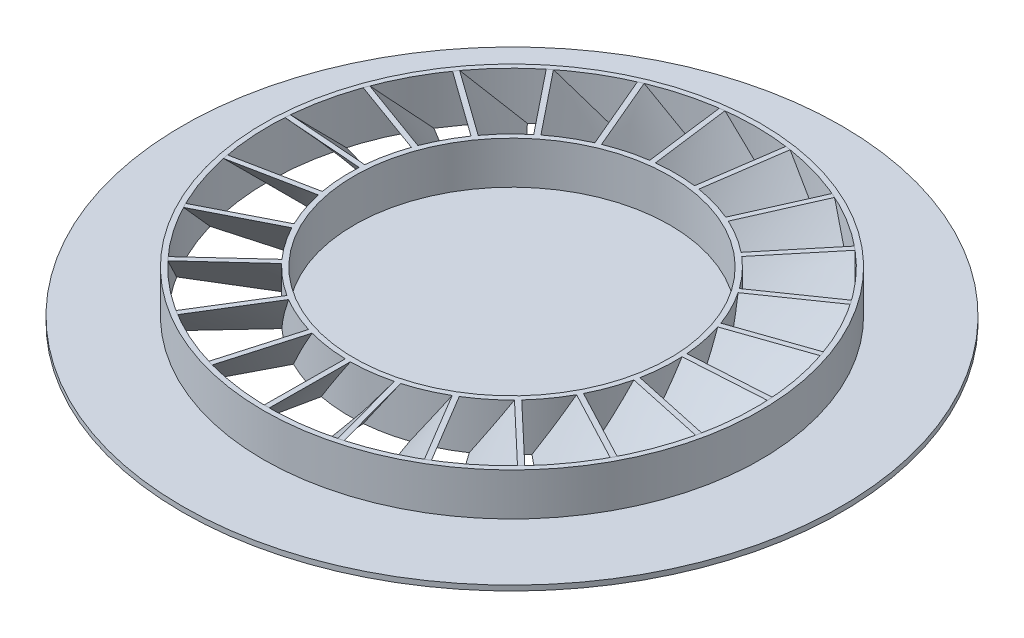
SolidWorks part; units mm, degrees
ref_plane "Front Plane" through (0, 0, 0) normal (0, 0, 1) x (1, 0, 0)
ref_plane "Top Plane" through (0, 0, 0) normal (0, 1, 0) x (1, 0, 0)
ref_plane "Right Plane" through (0, 0, 0) normal (1, 0, 0) x (0, 0, -1)
sketch "Sketch1" plane through (0, 0, 0) normal (0, 1, 0) x (1, 0, 0)
  circle A0 centre (0, 0) radius 33.25
  circle A1 centre (0, 0) radius 33.95
  circle A2 centre (0, 0) radius 45
  circle A3 centre (0, 0) radius 22.25
  circle A4 centre (0, 0) radius 21.55
  dimension "D1" = 66.5
  dimension "D2" = 0.7
  dimension "D3" = 90
  dimension "D4" = 44.5
  dimension "D5" = 0.7
extrude "Boss-Extrude1" add sketch "Sketch1" along normal blind 6.5 contours A1 A0 region at (-33.854, 0, 0)
extrude "Boss-Extrude2" add sketch "Sketch1<3>" along normal blind 0.7 contours A2 A1 region at (-43.7272, 0, 0)
sketch "Sketch1<3>" plane through (0, 0, 0) normal (0, 1, 0) x (1, 0, 0) same geometry as "Sketch1"
extrude "Boss-Extrude3" add sketch "Sketch1<4>" along normal blind 6.5 separate body contours A3 A4 region at (-21.6207, 0, 0)
sketch "Sketch1<4>" plane through (0, 0, 0) normal (0, 1, 0) x (1, 0, 0) same geometry as "Sketch1"
extrude "Boss-Extrude4" add sketch "Sketch1<5>" along normal blind 0.7 contours A4 region at (0, 0, 0)
sketch "Sketch1<5>" plane through (0, 0, 0) normal (0, 1, 0) x (1, 0, 0) same geometry as "Sketch1"
sketch "Sketch2" plane through (0, 0, 0) normal (0, -1, 0) x (1, 0, 0)
  line L0 (-31.9208, 9.3073) -> (-21.3278, 6.3393)
  line L1 (-33.2482, 0.35) -> (-22.2472, 0.35)
  line L2 (-33.2482, -0.35) -> (-22.2472, -0.35)
  line L3 (-32.1097, 8.6332) -> (-21.5167, 5.6652)
  line L4 (-28.226, 17.5743) -> (-18.8266, 11.8584)
  line L5 (-28.5897, 16.9762) -> (-19.1903, 11.2603)
  line L6 (-22.4378, 24.5378) -> (-14.9291, 16.498)
  line L7 (-22.9494, 24.0601) -> (-15.4407, 16.0202)
  line L8 (-14.9856, 29.6816) -> (-9.9244, 19.914)
  line L9 (-15.6071, 29.3595) -> (-10.5459, 19.592)
  line L10 (-6.4219, 32.624) -> (-4.1837, 21.8531)
  line L11 (-7.1072, 32.4815) -> (-4.869, 21.7107)
  line L12 (2.6181, 33.1468) -> (1.8674, 22.1715)
  line L13 (1.9198, 33.1945) -> (1.169, 22.2193)
  line L14 (11.4639, 31.2112) -> (7.7799, 20.8455)
  line L15 (10.8043, 31.4456) -> (7.1204, 21.0799)
  line L16 (19.4595, 26.9609) -> (13.1155, 17.9735)
  line L17 (18.8876, 27.3646) -> (12.5436, 18.3772)
  line L18 (26.0119, 20.711) -> (17.4783, 13.7685)
  line L19 (25.5701, 21.254) -> (17.0366, 14.3115)
  line L20 (30.635, 12.9251) -> (20.5449, 8.5423)
  line L21 (30.3561, 13.5671) -> (20.266, 9.1844)
  line L22 (32.9861, 4.1806) -> (22.0877, 2.6826)
  line L23 (32.8908, 4.874) -> (21.9924, 3.3761)
  line L24 (32.8908, -4.874) -> (21.9924, -3.3761)
  line L25 (32.9861, -4.1806) -> (22.0877, -2.6826)
  line L26 (30.3561, -13.5671) -> (20.266, -9.1844)
  line L27 (30.635, -12.9251) -> (20.5449, -8.5423)
  line L28 (25.5701, -21.254) -> (17.0366, -14.3115)
  line L29 (26.0119, -20.711) -> (17.4783, -13.7685)
  line L30 (18.8876, -27.3646) -> (12.5436, -18.3772)
  line L31 (19.4595, -26.9609) -> (13.1155, -17.9735)
  line L32 (10.8043, -31.4456) -> (7.1204, -21.0799)
  line L33 (11.4639, -31.2112) -> (7.7799, -20.8455)
  line L34 (1.9198, -33.1945) -> (1.169, -22.2193)
  line L35 (2.6181, -33.1468) -> (1.8674, -22.1715)
  line L36 (-7.1072, -32.4815) -> (-4.869, -21.7107)
  line L37 (-6.4219, -32.624) -> (-4.1837, -21.8531)
  line L38 (-15.6071, -29.3595) -> (-10.5459, -19.592)
  line L39 (-14.9856, -29.6816) -> (-9.9244, -19.914)
  line L40 (-22.9494, -24.0601) -> (-15.4407, -16.0202)
  line L41 (-22.4378, -24.5378) -> (-14.9291, -16.498)
  line L42 (-28.5897, -16.9762) -> (-19.1903, -11.2603)
  line L43 (-28.226, -17.5743) -> (-18.8266, -11.8584)
  line L44 (-32.1097, -8.6332) -> (-21.5167, -5.6652)
  line L45 (-31.9208, -9.3073) -> (-21.3278, -6.3393)
  circle A0 centre (0, 0) radius 33.25 construction
  circle A1 centre (0, 0) radius 22.25
  arc A2 (-21.3278, 6.3393) -> (-21.5167, 5.6652) centre (0, 0) ccw
  arc A3 (-18.8266, 11.8584) -> (-19.1903, 11.2603) centre (0, 0) ccw
  circle A5 centre (0, 0) radius 22.25 construction
  arc A6 (-31.9208, 9.3073) -> (-32.1097, 8.6332) centre (0, 0) ccw
  arc A7 (-28.226, 17.5743) -> (-28.5897, 16.9762) centre (0, 0) ccw
  arc A8 (-22.4378, 24.5378) -> (-22.9494, 24.0601) centre (0, 0) ccw
  arc A9 (-14.9291, 16.498) -> (-15.4407, 16.0202) centre (0, 0) ccw
  arc A10 (-9.9244, 19.914) -> (-10.5459, 19.592) centre (0, 0) ccw
  arc A11 (-14.9856, 29.6816) -> (-15.6071, 29.3595) centre (0, 0) ccw
  arc A12 (-6.4219, 32.624) -> (-7.1072, 32.4815) centre (0, 0) ccw
  arc A13 (-4.1837, 21.8531) -> (-4.869, 21.7107) centre (0, 0) ccw
  arc A14 (1.8674, 22.1715) -> (1.169, 22.2193) centre (0, 0) ccw
  arc A15 (2.6181, 33.1468) -> (1.9198, 33.1945) centre (0, 0) ccw
  arc A16 (11.4639, 31.2112) -> (10.8043, 31.4456) centre (0, 0) ccw
  arc A17 (7.7799, 20.8455) -> (7.1204, 21.0799) centre (0, 0) ccw
  arc A18 (13.1155, 17.9735) -> (12.5436, 18.3772) centre (0, 0) ccw
  arc A19 (19.4595, 26.9609) -> (18.8876, 27.3646) centre (0, 0) ccw
  arc A20 (26.0119, 20.711) -> (25.5701, 21.254) centre (0, 0) ccw
  arc A21 (17.4783, 13.7685) -> (17.0366, 14.3115) centre (0, 0) ccw
  arc A22 (20.5449, 8.5423) -> (20.266, 9.1844) centre (0, 0) ccw
  arc A23 (30.635, 12.9251) -> (30.3561, 13.5671) centre (0, 0) ccw
  arc A24 (32.9861, 4.1806) -> (32.8908, 4.874) centre (0, 0) ccw
  arc A25 (22.0877, 2.6826) -> (21.9924, 3.3761) centre (0, 0) ccw
  arc A26 (21.9924, -3.3761) -> (22.0877, -2.6826) centre (0, 0) ccw
  arc A27 (32.8908, -4.874) -> (32.9861, -4.1806) centre (0, 0) ccw
  arc A28 (-22.2472, 0.35) -> (-22.2472, -0.35) centre (0, 0) ccw
  arc A29 (-33.2482, 0.35) -> (-33.2482, -0.35) centre (0, 0) ccw
  arc A30 (-21.5167, -5.6652) -> (-21.3278, -6.3393) centre (0, 0) ccw
  arc A31 (-32.1097, -8.6332) -> (-31.9208, -9.3073) centre (0, 0) ccw
  arc A32 (-19.1903, -11.2603) -> (-18.8266, -11.8584) centre (0, 0) ccw
  arc A33 (-28.5897, -16.9762) -> (-28.226, -17.5743) centre (0, 0) ccw
  arc A34 (-22.9494, -24.0601) -> (-22.4378, -24.5378) centre (0, 0) ccw
  arc A35 (-15.4407, -16.0202) -> (-14.9291, -16.498) centre (0, 0) ccw
  arc A36 (-10.5459, -19.592) -> (-9.9244, -19.914) centre (0, 0) ccw
  arc A37 (-15.6071, -29.3595) -> (-14.9856, -29.6816) centre (0, 0) ccw
  arc A38 (-7.1072, -32.4815) -> (-6.4219, -32.624) centre (0, 0) ccw
  arc A39 (-4.869, -21.7107) -> (-4.1837, -21.8531) centre (0, 0) ccw
  arc A40 (1.169, -22.2193) -> (1.8674, -22.1715) centre (0, 0) ccw
  arc A41 (1.9198, -33.1945) -> (2.6181, -33.1468) centre (0, 0) ccw
  arc A42 (10.8043, -31.4456) -> (11.4639, -31.2112) centre (0, 0) ccw
  arc A43 (7.1204, -21.0799) -> (7.7799, -20.8455) centre (0, 0) ccw
  arc A44 (12.5436, -18.3772) -> (13.1155, -17.9735) centre (0, 0) ccw
  arc A45 (18.8876, -27.3646) -> (19.4595, -26.9609) centre (0, 0) ccw
  arc A46 (25.5701, -21.254) -> (26.0119, -20.711) centre (0, 0) ccw
  arc A47 (17.0366, -14.3115) -> (17.4783, -13.7685) centre (0, 0) ccw
  arc A48 (20.266, -9.1844) -> (20.5449, -8.5423) centre (0, 0) ccw
  arc A49 (30.3561, -13.5671) -> (30.635, -12.9251) centre (0, 0) ccw
  point P2 (-25.0222, 7.7008)
  point P14 (0, 0)
  point P106 (0, 0)
  dimension "D3" = 0.7
  dimension "D1" = 0
  dimension "D4" = 23
sketch "Sketch3" plane through (0, 6.5, 0) normal (0, 1, 0) x (1, 0, 0)
  line L0 (0, 0) -> (-32.6054, -6.5152) construction
  line L1 (0, 0) -> (-15.6581, 0) construction
  line L2 (-21.8846, -4.016) -> (-32.6722, -6.1716)
  line L3 (-21.7474, -4.7025) -> (-32.535, -6.8581)
  line L4 (-22.1565, 2.0373) -> (-33.1257, 2.8721)
  line L5 (-22.2097, 1.3393) -> (-33.1788, 2.1741)
  line L6 (-20.7853, 7.9395) -> (-31.1225, 11.7028)
  line L7 (-21.0247, 7.2817) -> (-31.3619, 11.045)
  line L8 (-17.8724, 13.2529) -> (-26.811, 19.6656)
  line L9 (-18.2805, 12.6841) -> (-27.219, 19.0968)
  line L10 (-13.6341, 17.5833) -> (-20.511, 26.1698)
  line L11 (-14.1805, 17.1457) -> (-21.0574, 25.7322)
  line L12 (-8.3846, 20.6097) -> (-12.6899, 30.7332)
  line L13 (-9.0288, 20.3358) -> (-13.3341, 30.4592)
  line L14 (-2.5132, 22.1076) -> (-3.9276, 33.0172)
  line L15 (-3.2074, 22.0176) -> (-4.6218, 32.9272)
  line L16 (3.5445, 21.9659) -> (5.126, 32.8525)
  line L17 (2.8518, 22.0665) -> (4.4332, 32.9531)
  line L18 (9.3394, 20.195) -> (13.7994, 30.2513)
  line L19 (8.6995, 20.4788) -> (13.1595, 30.5351)
  line L20 (14.4416, 16.9264) -> (21.4494, 25.4064)
  line L21 (13.902, 17.3723) -> (20.9098, 25.8524)
  line L22 (18.4728, 12.4024) -> (27.5085, 18.6773)
  line L23 (18.0735, 12.9774) -> (27.1093, 19.2523)
  line L24 (21.1339, 6.9586) -> (31.5275, 10.563)
  line L25 (20.9045, 7.6199) -> (31.2982, 11.2244)
  line L26 (22.2276, 0.9987) -> (33.2083, 1.6653)
  line L27 (22.1852, 1.6974) -> (33.1659, 2.364)
  line L28 (21.6728, -5.0353) -> (32.4261, -7.356)
  line L29 (21.8204, -4.351) -> (32.5738, -6.6717)
  line L30 (19.5106, -10.6958) -> (29.239, -15.8316)
  line L31 (19.8374, -10.0768) -> (29.5658, -15.2126)
  line L32 (15.9014, -15.563) -> (23.8835, -23.1332)
  line L33 (16.3831, -15.0551) -> (24.3652, -22.6252)
  line L34 (11.1129, -19.2761) -> (16.7565, -28.719)
  line L35 (11.7137, -18.917) -> (17.3574, -28.3599)
  line L36 (5.5001, -21.5595) -> (8.3869, -32.1749)
  line L37 (6.1756, -21.3758) -> (9.0623, -31.9912)
  line L38 (-0.5205, -22.2439) -> (-0.6048, -33.2445)
  line L39 (0.1795, -22.2493) -> (0.0952, -33.2499)
  line L40 (-6.5025, -21.2786) -> (-9.5516, -31.8485)
  line L41 (-5.83, -21.4726) -> (-8.8791, -32.0425)
  line L42 (-12.0023, -18.7352) -> (-17.7901, -28.0905)
  line L43 (-11.407, -19.1035) -> (-17.1948, -28.4588)
  line L44 (-16.6119, -14.8023) -> (-24.7091, -22.2491)
  line L45 (-16.1381, -15.3175) -> (-24.2352, -22.7644)
  line L46 (-19.9895, -9.7715) -> (-29.7956, -14.7576)
  line L47 (-19.6722, -10.3955) -> (-29.4783, -15.3816)
  circle A0 centre (0, 0) radius 33.25 construction
  circle A1 centre (0, 0) radius 22.25 construction
  arc A2 (-32.6722, -6.1716) -> (-32.535, -6.8581) centre (0, 0) ccw
  arc A3 (-21.8846, -4.016) -> (-21.7474, -4.7025) centre (0, 0) ccw
  arc A4 (-22.1565, 2.0373) -> (-22.2097, 1.3393) centre (0, 0) ccw
  arc A5 (-33.1257, 2.8721) -> (-33.1788, 2.1741) centre (0, 0) ccw
  arc A6 (-20.7853, 7.9395) -> (-21.0247, 7.2817) centre (0, 0) ccw
  arc A7 (-31.1225, 11.7028) -> (-31.3619, 11.045) centre (0, 0) ccw
  arc A8 (-17.8724, 13.2529) -> (-18.2805, 12.6841) centre (0, 0) ccw
  arc A9 (-26.811, 19.6656) -> (-27.219, 19.0968) centre (0, 0) ccw
  arc A10 (-13.6341, 17.5833) -> (-14.1805, 17.1457) centre (0, 0) ccw
  arc A11 (-20.511, 26.1698) -> (-21.0574, 25.7322) centre (0, 0) ccw
  arc A12 (-8.3846, 20.6097) -> (-9.0288, 20.3358) centre (0, 0) ccw
  arc A13 (-12.6899, 30.7332) -> (-13.3341, 30.4592) centre (0, 0) ccw
  arc A14 (-2.5132, 22.1076) -> (-3.2074, 22.0176) centre (0, 0) ccw
  arc A15 (-3.9276, 33.0172) -> (-4.6218, 32.9272) centre (0, 0) ccw
  arc A16 (3.5445, 21.9659) -> (2.8518, 22.0665) centre (0, 0) ccw
  arc A17 (5.126, 32.8525) -> (4.4332, 32.9531) centre (0, 0) ccw
  arc A18 (9.3394, 20.195) -> (8.6995, 20.4788) centre (0, 0) ccw
  arc A19 (13.7994, 30.2513) -> (13.1595, 30.5351) centre (0, 0) ccw
  arc A20 (14.4416, 16.9264) -> (13.902, 17.3723) centre (0, 0) ccw
  arc A21 (21.4494, 25.4064) -> (20.9098, 25.8524) centre (0, 0) ccw
  arc A22 (18.4728, 12.4024) -> (18.0735, 12.9774) centre (0, 0) ccw
  arc A23 (27.5085, 18.6773) -> (27.1093, 19.2523) centre (0, 0) ccw
  arc A24 (21.1339, 6.9586) -> (20.9045, 7.6199) centre (0, 0) ccw
  arc A25 (31.5275, 10.563) -> (31.2982, 11.2244) centre (0, 0) ccw
  arc A26 (22.2276, 0.9987) -> (22.1852, 1.6974) centre (0, 0) ccw
  arc A27 (33.2083, 1.6653) -> (33.1659, 2.364) centre (0, 0) ccw
  arc A28 (21.6728, -5.0353) -> (21.8204, -4.351) centre (0, 0) ccw
  arc A29 (32.4261, -7.356) -> (32.5738, -6.6717) centre (0, 0) ccw
  arc A30 (19.5106, -10.6958) -> (19.8374, -10.0768) centre (0, 0) ccw
  arc A31 (29.239, -15.8316) -> (29.5658, -15.2126) centre (0, 0) ccw
  arc A32 (15.9014, -15.563) -> (16.3831, -15.0551) centre (0, 0) ccw
  arc A33 (23.8835, -23.1332) -> (24.3652, -22.6252) centre (0, 0) ccw
  arc A34 (11.1129, -19.2761) -> (11.7137, -18.917) centre (0, 0) ccw
  arc A35 (16.7565, -28.719) -> (17.3574, -28.3599) centre (0, 0) ccw
  arc A36 (5.5001, -21.5595) -> (6.1756, -21.3758) centre (0, 0) ccw
  arc A37 (8.3869, -32.1749) -> (9.0623, -31.9912) centre (0, 0) ccw
  arc A38 (-0.5205, -22.2439) -> (0.1795, -22.2493) centre (0, 0) ccw
  arc A39 (-0.6048, -33.2445) -> (0.0952, -33.2499) centre (0, 0) ccw
  arc A40 (-6.5025, -21.2786) -> (-5.83, -21.4726) centre (0, 0) ccw
  arc A41 (-9.5516, -31.8485) -> (-8.8791, -32.0425) centre (0, 0) ccw
  arc A42 (-12.0023, -18.7352) -> (-11.407, -19.1035) centre (0, 0) ccw
  arc A43 (-17.7901, -28.0905) -> (-17.1948, -28.4588) centre (0, 0) ccw
  arc A44 (-16.6119, -14.8023) -> (-16.1381, -15.3175) centre (0, 0) ccw
  arc A45 (-24.7091, -22.2491) -> (-24.2352, -22.7644) centre (0, 0) ccw
  arc A46 (-19.9895, -9.7715) -> (-19.6722, -10.3955) centre (0, 0) ccw
  arc A47 (-29.7956, -14.7576) -> (-29.4783, -15.3816) centre (0, 0) ccw
  point P101 (0, 0)
  dimension "D1" = 11.3
  dimension "D2" = 0.35
  dimension "D3" = 0.35
  dimension "D4" = 23
loft "Loft1" add section "Sketch2" section "Sketch3" connector at (-32.1097, 0, 8.6332) connector at (-29.7956, 6.5, 14.7576)
pattern_circular "CirPattern1" count 23 over 360 about axis through (0, 6.5, 0) along (0, -1, 0) of "Loft1"
